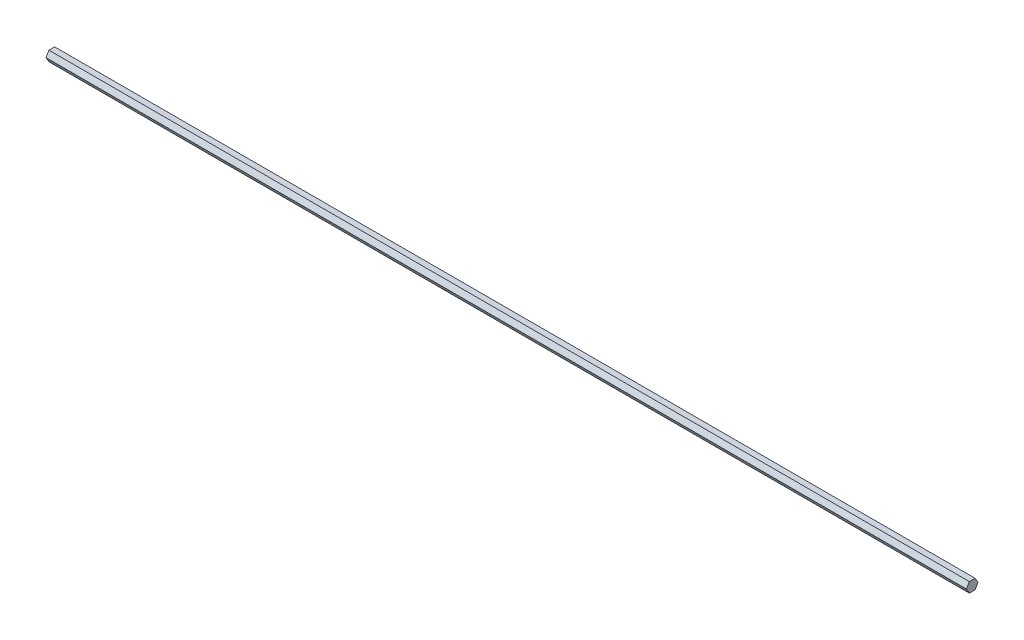
SolidWorks part; units mm, degrees
ref_plane "Front Plane" through (0, 0, 0) normal (0, 0, 1) x (1, 0, 0)
ref_plane "Top Plane" through (0, 0, 0) normal (0, 1, 0) x (1, 0, 0)
ref_plane "Right Plane" through (0, 0, 0) normal (1, 0, 0) x (0, 0, -1)
sketch "Sketch1" plane through (0, 0, 0) normal (1, 0, 0) x (0, 0, -1)
  line L1 (1.5, 0) -> (0.75, 1.299)
  line L2 (0.75, 1.299) -> (-0.75, 1.299)
  line L3 (-0.75, 1.299) -> (-1.5, 0)
  line L4 (-1.5, 0) -> (-0.75, -1.299)
  line L5 (-0.75, -1.299) -> (0.75, -1.299)
  line L6 (0.75, -1.299) -> (1.5, 0)
  circle A0 centre (0, 0) radius 1.299 construction
  dimension "D1" = 3
extrude "Boss-Extrude1" add sketch "Sketch1" along normal mid plane 238.76
ref_axis "Drive Axis" through (-131.318, 0, 0) along (1, 0, 0)
